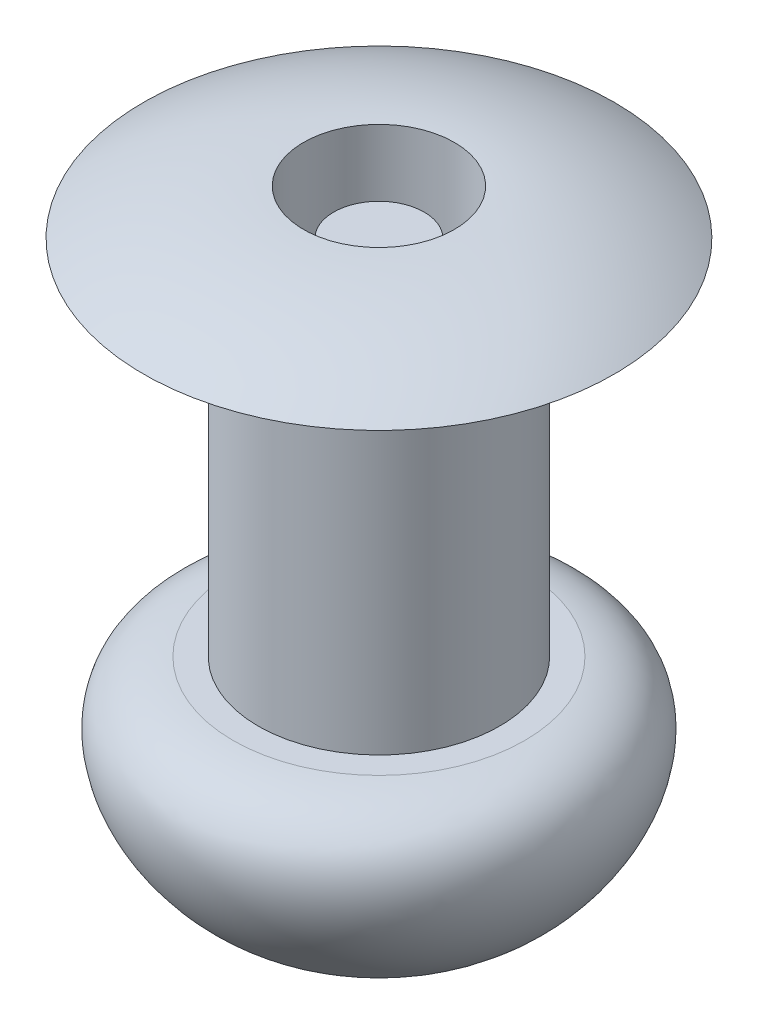
SolidWorks part; units mm, degrees
material "AISI 316 Stal nierdzewna odprężona (SS)"
ref_plane "Płaszczyzna przednia" through (0, 0, 0) normal (0, 0, 1) x (1, 0, 0)
ref_plane "Płaszczyzna górna" through (0, 0, 0) normal (0, 1, 0) x (1, 0, 0)
ref_plane "Płaszczyzna prawa" through (0, 0, 0) normal (1, 0, 0) x (0, 0, -1)
sketch "Szkic1" plane through (0, 0, 0) normal (1, 0, 0) x (0, 0, -1)
  line L0 (0, 0) -> (0, -6)
  line L1 (0, 0) -> (-0.75, 0)
  line L2 (-0.75, 0) -> (-0.75, -6)
  line L3 (-0.75, -6) -> (-1.25, -6)
  line L4 (-1.25, -6) -> (-1.25, 0.75)
  line L5 (-3.9, 0) -> (-2, 0)
  line L6 (-2, 0) -> (-2, -6)
  line L7 (-2, -6) -> (-2.4139, -6)
  line L8 (0, 0) -> (0, 0.4842) construction
  line L10 (0, -6) -> (0, -7.5)
  arc A0 (-1.25, 0.75) -> (-3.9, 0) centre (-1.25, -4.3067) ccw
  ellipse E0 centre (0, -6.75) end of major axis (-1.75, -6.75) minor radius 0.75 (-0.956, -7.3782) -> (0, -7.5) ccw
  spline S0 degree 3 poles (-2.4139, -6) (-3.8586, -6.1633) (-3.5584, -8.323) (-0.9713, -9.8719) (-0.3411, -7.792) (-0.956, -7.3782) knots 0 0 0 0 0.454219 0.705201 1 1 1 1
  dimension "D1" = 7.8
  dimension "D2" = 2.5
  dimension "D3" = 4
  dimension "D4" = 0.75
  dimension "D5" = 1.5
  dimension "D6" = 1.5
  dimension "D7" = 3.5
  dimension "D8" = 3.1855
  dimension "D9" = 2.5026
  dimension "D10" = 1.9
  dimension "D11" = 1.3782
  dimension "D12" = 0.5792
  dimension "D13" = 4.8278
  dimension "D14" = 3.3858
  dimension "D15" = 2.8395
  dimension "D16" = 1.25
  dimension "D17" = 0.6409
  dimension "D18" = 0.956
  dimension "D19" = 6
revolve "Obrót1" add sketch "Szkic1" angle 360 about L8
